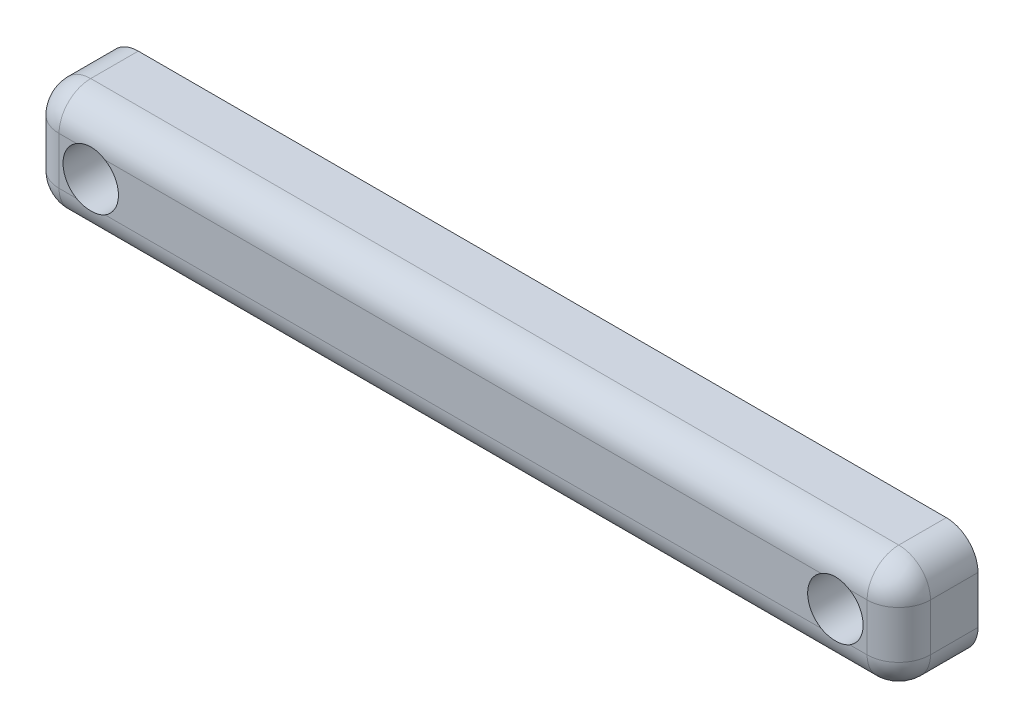
SolidWorks part; units mm, degrees
ref_plane "Front Plane" through (0, 0, 0) normal (0, 0, 1) x (1, 0, 0)
ref_plane "Top Plane" through (0, 0, 0) normal (0, 1, 0) x (1, 0, 0)
ref_plane "Right Plane" through (0, 0, 0) normal (1, 0, 0) x (0, 0, -1)
sketch "Sketch1" plane through (0, 0, 0) normal (0, 0, 1) x (1, 0, 0)
  line L0 (-23.5, 0) -> (23.5, 0) construction
  line L1 (-25.5, 3.5) -> (25.5, 3.5)
  line L2 (-27.5, 1.5) -> (-27.5, -1.5)
  line L3 (-25.5, -3.5) -> (25.5, -3.5)
  line L4 (27.5, 1.5) -> (27.5, -1.5)
  line L5 (-27.5, 3.5) -> (27.5, -3.5) construction
  line L6 (-27.5, -3.5) -> (27.5, 3.5) construction
  circle A0 centre (-23.5, 0) radius 1.75
  circle A1 centre (23.5, 0) radius 1.75
  arc A2 (25.5, 3.5) -> (27.5, 1.5) centre (25.5, 1.5) cw
  arc A3 (25.5, -3.5) -> (27.5, -1.5) centre (25.5, -1.5) ccw
  arc A4 (-27.5, -1.5) -> (-25.5, -3.5) centre (-25.5, -1.5) ccw
  arc A5 (-25.5, 3.5) -> (-27.5, 1.5) centre (-25.5, 1.5) ccw
  point P0 (0, 0)
  dimension "D3" = 3.5
  dimension "D5" = 2
  dimension "D6" = 3.5
  dimension "D1" = 7
  dimension "D2" = 55
  dimension "D4" = 4
extrude "Boss-Extrude1" add sketch "Sketch1" along normal blind 5
fillet "Fillet1" radius 2 8 edges at (26.9142, 2.9142, 5) (27.5, 0, 5) (26.9142, -2.9142, 5) (0, -3.5, 5) (-26.9142, -2.9142, 5) (-27.5, 0, 5) (-26.9142, 2.9142, 5) (0, 3.5, 5)
